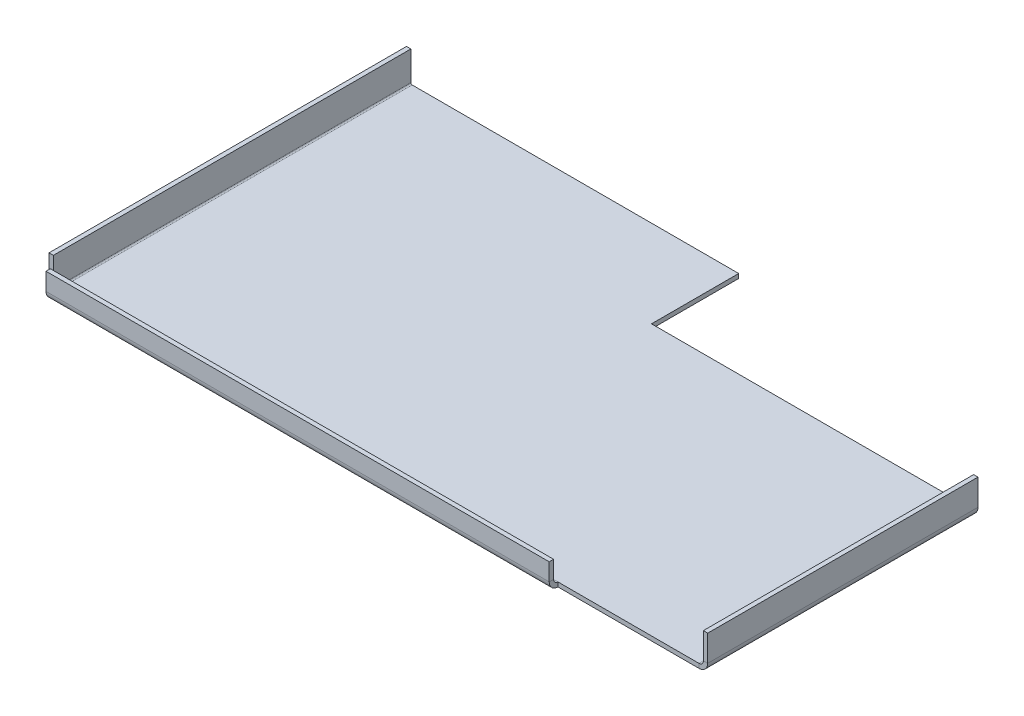
SolidWorks part; units mm, degrees
note: The reader was unsure of these and kept them because the rebuilt part matched: thickness of "Base-Flange1", "Edge-Flange1", "Edge-Flange2", "Edge-Flange3", "Sheet-Metal3", "Sheet-Metal5", "Sheet-Metal6", "Sheet-Metal7", "Sheet-Metal8"; flange length of "Edge-Flange1", "Edge-Flange2", "Edge-Flange3".
material "6061-T6 (SS)"
ref_plane "X-Y Datum" through (0, 0, 0) normal (0, 0, 1) x (1, 0, 0)
ref_plane "X-Z Datum" through (0, 0, 0) normal (0, 1, 0) x (1, 0, 0)
ref_plane "Y-Z Datum" through (0, 0, 0) normal (1, 0, 0) x (0, 0, -1)
sketch "Sketch1" plane through (0, 0, 0) normal (0, 1, 0) x (1, 0, 0)
  line L1 (-232.0925, 63.7857) -> (232.0925, 63.7857)
  line L2 (-232.0925, 63.7857) -> (-232.0925, -63.7858)
  line L3 (-232.0925, -63.7858) -> (232.0925, -63.7858)
  line L4 (232.0925, 63.7857) -> (232.0925, -63.7858)
  line L5 (-232.0925, 63.7857) -> (232.0925, -63.7858) construction
  line L6 (-232.0925, -63.7858) -> (232.0925, 63.7857) construction
  point P0 (0, 0)
  dimension "D1" = 464.185
  dimension "D2" = 127.5715
sketch "Sketch2" plane through (0, 0, 0) normal (0, 1, 0) x (1, 0, 0)
  line L0 (-232.0925, 63.7857) -> (232.0925, 63.7857)
  line L1 (232.0925, 63.7857) -> (232.0925, 152.6857)
  line L2 (232.0925, 152.6857) -> (-155.8925, 152.6857)
  line L3 (-155.8925, 152.6857) -> (-232.0925, 76.4857)
  line L4 (-232.0925, 76.4857) -> (-232.0925, 63.7857)
  dimension "D1" = 45
  dimension "D2" = 12.7
  dimension "D3" = 88.9
sketch "Sketch5" plane through (0, 0, 0) normal (0, 1, 0) x (1, 0, 0)
  line L1 (-237.7745, 130.175) -> (237.7745, 130.175)
  line L2 (-237.7745, 130.175) -> (-237.7745, -130.175)
  line L3 (-237.7745, -130.175) -> (237.7745, -130.175)
  line L4 (237.7745, 130.175) -> (237.7745, -130.175)
  line L5 (-237.7745, 130.175) -> (237.7745, -130.175) construction
  line L6 (-237.7745, -130.175) -> (237.7745, 130.175) construction
  point P0 (0, 0)
  dimension "D1" = 475.549
  dimension "D2" = 260.35
base flange "Base-Flange1" sketch "Sketch5" thickness 3.175 reverse thickness direction no parameters "D1"=1
edge flange "Edge-Flange1" sketch "Sketch8" flange angle 90 flange length 19.05 flange position bend outside bend radius 3.175 thickness 3.175 relief rectangular parameters "D6"=10
sketch "Sketch8" plane through (0, 0, 130.175) normal (0, 0, 1) x (1, 0, 0)
  line L0 (-237.7745, 0) -> (237.7745, 0) construction
  line L2 (-237.7745, 0) -> (-237.7745, 15.875)
  line L3 (-237.7745, 15.875) -> (128.7069, 15.875)
  line L5 (-237.7745, 0) -> (128.7069, 0)
  line L10 (128.7069, 15.875) -> (128.7069, 0)
bend "EdgeBend1" bend radius 3.175 bend angle 90 parameters "D5"=1
edge flange "Edge-Flange2" sketch "Sketch11" flange angle 90 flange length 25.4 flange position material inside bend radius 3.175 thickness 3.175 relief rectangular parameters "D6"=10
sketch "Sketch11" plane through (237.7745, 0, 0) normal (-1, 0, 0) x (0, 0, 1)
  line L0 (130.175, 0) -> (-130.175, 0) construction
  line L2 (-130.175, 0) -> (-130.175, 22.225)
  line L3 (-130.175, 22.225) -> (130.175, 22.225)
  line L4 (130.175, 22.225) -> (130.175, 0)
  line L5 (130.175, 0) -> (-130.175, 0)
bend "EdgeBend2" bend radius 3.175 bend angle 90 parameters "D5"=2
edge flange "Edge-Flange3" sketch "Sketch14" flange angle 90 flange length 25.4 flange position bend outside bend radius 1 thickness 3.175 relief rectangular parameters "D6"=10
sketch "Sketch14" plane through (-237.7745, 0, 0) normal (1, 0, 0) x (0, 0, -1)
  line L0 (130.175, 0) -> (-130.175, 0) construction
  line L2 (-130.175, 0) -> (-130.175, 22.225)
  line L3 (-130.175, 22.225) -> (130.175, 22.225)
  line L4 (130.175, 22.225) -> (130.175, 0)
  line L5 (130.175, 0) -> (-130.175, 0)
bend "EdgeBend3" bend radius 1 bend angle 90 parameters "D5"=3
sketch "Sketch16" plane through (0, 0, 0) normal (0, 1, 0) x (1, 0, 0)
  line L0 (0, 188.9559) -> (0, 66.675)
  line L1 (0, 66.675) -> (336.9384, 66.675)
  line L2 (336.9384, 66.675) -> (336.9384, 188.9559)
  line L3 (336.9384, 188.9559) -> (0, 188.9559)
  line L5 (231.4245, 130.175) -> (-237.7745, 130.175) construction
  line L6 (0, -43.0151) -> (0, 43.0151) construction
  dimension "D1" = 63.5
extrude "Cut-Extrude1" cut sketch "Sketch16" against normal through all both and the other way through all normal cut yes
sketch "Bend-Lines1" [suppressed] plane through (0, 0, 0) normal (0, 1, 0) x (1, 0, 0)
sketch "Bounding-Box1" [suppressed] plane through (0, 0, 0) normal (0, 1, 0) x (1, 0, 0)
sheet metal parameters "Sheet-Metal3" thickness 3.175 parameters "D1"=1
flat pattern "Flat-Pattern3" [suppressed]
sketch "Bend-Lines2" plane through (0, 0, 0) normal (0, 1, 0) x (1, 0, 0)
sketch3d "Bounding-Box2" [suppressed]
  line L0 (235.4174, -63.7858, 0) -> (-235.4174, -63.7858, 0) construction
  line L1 (235.4174, 63.7858, 0) -> (-235.4174, 63.7858, 0) construction
  line L2 (235.4174, -63.7858, 0) -> (235.4174, 63.7858, 0) construction
  line L3 (-235.4174, -63.7858, 0) -> (-235.4174, 63.7858, 0) construction
sheet metal parameters "Sheet-Metal5" thickness 3.175 parameters "D1"=1
flat pattern "Flat-Pattern3"
sketch "Bend-Lines2" plane through (0, 0, 0) normal (0, 1, 0) x (1, 0, 0)
  line L0 (-235.4174, -67.5262) -> (128.7069, -67.5262) construction
  line L1 (-235.4174, -67.5262) -> (128.7069, -67.5262) construction
sketch3d "Bounding-Box2" [suppressed]
  line L0 (235.4174, -83.9667, 0) -> (-235.4174, -83.9667, 0) construction
  line L1 (235.4174, 63.7858, 0) -> (-235.4174, 63.7858, 0) construction
  line L2 (235.4174, -83.9667, 0) -> (235.4174, 63.7858, 0) construction
  line L3 (-235.4174, -83.9667, 0) -> (-235.4174, 63.7858, 0) construction
bend of the flat pattern "Flatten-<EdgeBend1>1"
sheet metal parameters "Sheet-Metal6" thickness 3.175 parameters "D1"=1
flat pattern "Flat-Pattern3"
sketch "Bend-Lines2" plane through (0, 0, 0) normal (0, 1, 0) x (1, 0, 0)
  line L0 (-235.4174, -67.5262) -> (128.7069, -67.5262) construction
  line L1 (-235.4174, -67.5262) -> (128.7069, -67.5262) construction
  line L2 (232.8078, -63.7858) -> (232.8078, 63.7857) construction
  line L3 (232.8078, -63.7858) -> (232.8078, 63.7857) construction
sketch3d "Bounding-Box2" [suppressed]
  line L0 (255.5983, -83.9667, 0) -> (-235.4174, -83.9667, 0) construction
  line L1 (255.5983, 63.7858, 0) -> (-235.4174, 63.7858, 0) construction
  line L2 (255.5983, -83.9667, 0) -> (255.5983, 63.7858, 0) construction
  line L3 (-235.4174, -83.9667, 0) -> (-235.4174, 63.7858, 0) construction
bend of the flat pattern "Flatten-<EdgeBend1>1"
bend of the flat pattern "Flatten-<EdgeBend2>1"
sheet metal parameters "Sheet-Metal7" thickness 3.175 parameters "D1"=1
flat pattern "Flat-Pattern3"
sketch "Bend-Lines2" plane through (0, 0, 0) normal (0, 1, 0) x (1, 0, 0)
  line L0 (-237.7745, -133.9155) -> (128.7069, -133.9155) construction
  line L1 (-237.7745, -133.9155) -> (128.7069, -133.9155) construction
  line L2 (235.1649, -130.175) -> (235.1649, 130.175) construction
  line L3 (235.1649, -130.175) -> (235.1649, 130.175) construction
  line L4 (-239.8067, 130.175) -> (-239.8067, -130.175) construction
  line L5 (-239.8067, 130.175) -> (-239.8067, -130.175) construction
sketch3d "Bounding-Box2" [suppressed]
  line L0 (257.9554, -150.3559, 0) -> (-263.0639, -150.3559, 0) construction
  line L1 (257.9554, 130.175, 0) -> (-263.0639, 130.175, 0) construction
  line L2 (257.9554, -150.3559, 0) -> (257.9554, 130.175, 0) construction
  line L3 (-263.0639, -150.3559, 0) -> (-263.0639, 130.175, 0) construction
bend of the flat pattern "Flatten-<EdgeBend1>1"
bend of the flat pattern "Flatten-<EdgeBend2>1"
bend of the flat pattern "Flatten-<EdgeBend3>1"
sheet metal parameters "Sheet-Metal8" thickness 3.175 parameters "D1"=1
flat pattern "Flat-Pattern3"
sketch "Bend-Lines2" plane through (0, 0, 0) normal (0, 1, 0) x (1, 0, 0)
  line L0 (-237.7745, -133.9155) -> (128.7069, -133.9155) construction
  line L1 (-237.7745, -133.9155) -> (128.7069, -133.9155) construction
  line L2 (235.1649, -130.175) -> (235.1649, 66.675) construction
  line L3 (235.1649, -130.175) -> (235.1649, 66.675) construction
  line L4 (-239.8067, 130.175) -> (-239.8067, -130.175) construction
  line L5 (-239.8067, 130.175) -> (-239.8067, -130.175) construction
sketch3d "Bounding-Box2" [suppressed]
  line L0 (257.9554, -150.3559, 0) -> (-263.0639, -150.3559, 0) construction
  line L1 (257.9554, 130.175, 0) -> (-263.0639, 130.175, 0) construction
  line L2 (257.9554, -150.3559, 0) -> (257.9554, 130.175, 0) construction
  line L3 (-263.0639, -150.3559, 0) -> (-263.0639, 130.175, 0) construction
bend of the flat pattern "Flatten-<EdgeBend1>1"
bend of the flat pattern "Flatten-<EdgeBend2>1"
bend of the flat pattern "Flatten-<EdgeBend3>1"
